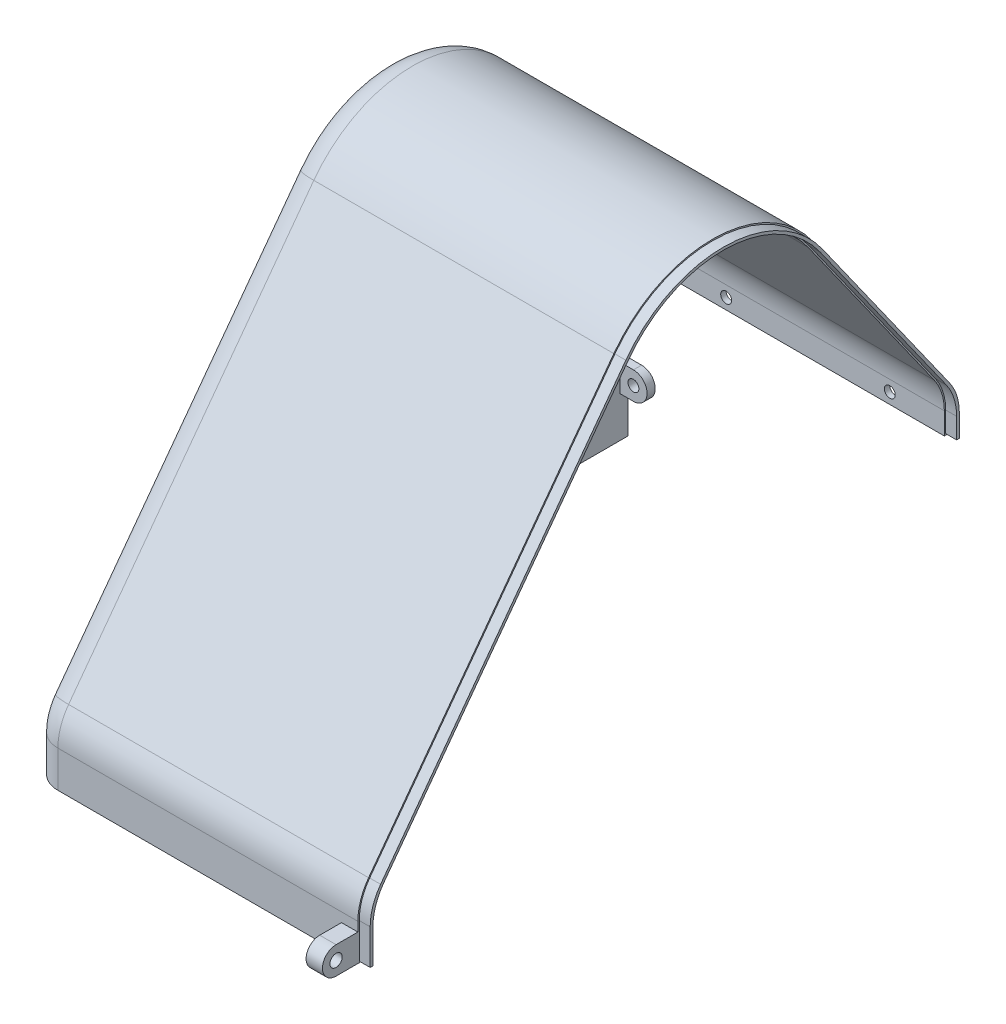
SolidWorks part; units mm, degrees
ref_plane "Alzado" through (0, 0, 0) normal (0, 0, 1) x (1, 0, 0)
ref_plane "Planta" through (0, 0, 0) normal (0, 1, 0) x (1, 0, 0)
ref_plane "Vista lateral" through (0, 0, 0) normal (1, 0, 0) x (0, 0, -1)
sketch "Croquis1" plane through (0, 0, 0) normal (1, 0, 0) x (0, 0, -1)
  line L0 (-200, 0) -> (200, 0)
  line L2 (17.0234, 70) -> (175, 70)
  line L3 (-200, 0) -> (-200, 20)
  line L4 (-200, 20) -> (-106.1703, 146.7714)
  line L5 (200, 0) -> (200, 45)
  line L6 (200, 45) -> (175, 70)
  line L7 (17.0234, 70) -> (17.0234, 75)
  line L8 (17.0234, 75) -> (-33.2796, 146.0118)
  arc A0 (-33.2796, 146.0118) -> (-106.1703, 146.7714) centre (-70, 120) ccw
  circle A1 centre (-70, 120) radius 12
  arc A3 (-106.1703, 146.7714) -> (-33.2796, 146.0118) centre (-70, 120) ccw construction
  point P3 (0, 0)
  dimension "D4" = 90
  dimension "D5" = 24
  dimension "D1" = 400
  dimension "D2" = 120
  dimension "D3" = 70
  dimension "D6" = 20
  dimension "D7" = 70
  dimension "D8" = 45
  dimension "D9" = 50.3031
  dimension "D10" = 45
  dimension "D11" = 5
extrude "Saliente-Extruir1" add sketch "Croquis1" along normal blind 120
sketch "Croquis2" plane through (120, 0, 0) normal (1, 0, 0) x (0, 0, -1)
  line L2 (200, 45) -> (175, 70) construction
  line L3 (35.0234, 60) -> (35.0234, 68)
  line L4 (35.0234, 68) -> (174.1716, 68)
  line L5 (175, 70) -> (17.0234, 70) construction
  line L7 (200, 0) -> (200, 45) construction
  line L8 (-198, 0) -> (-198, 19.3404)
  line L9 (-200, 0) -> (200, 0) construction
  line L20 (-198, 19.3404) -> (-104.5627, 145.5816)
  line L21 (-106.1703, 146.7714) -> (-200, 20) construction
  line L22 (-200, 20) -> (-200, 0) construction
  line L23 (-34.9117, 144.8557) -> (15.0234, 74.3634)
  line L24 (15.0234, 74.3634) -> (15.0234, 60)
  line L28 (15.0234, 60) -> (35.0234, 60)
  line L29 (174.1716, 68) -> (198, 44.1716)
  line L33 (198, 44.1716) -> (198, 0)
  line L34 (198, 0) -> (-198, 0)
  line L35 (17.0234, 70) -> (17.0234, 75) construction
  arc A8 (-34.9117, 144.8557) -> (-104.5627, 145.5816) centre (-70, 120) ccw
  arc A9 (-34.9117, 144.8557) -> (-104.5627, 145.5816) centre (-70, 120) ccw
  dimension "D2" = 2
  dimension "D3" = 2
  dimension "D4" = 2
  dimension "D5" = 2
  dimension "D6" = 2
  dimension "D7" = 10
  dimension "D8" = 20
  dimension "D1" = 2
extrude "Cortar-Extruir1" cut sketch "Croquis2" against normal offset from surface (118 mm away) 2 up to face at (0, 65.7099, -7.7545)
fillet "Redondeo1" radius 20 6 edges at (60, 45, -200) (60, 70, -175) (60, 20, 200) (61, 68, -174.1716) (61, 44.1716, -198) (61, 19.3404, 198)
sketch "Croquis3" plane through (0, 0, -17.0234) normal (0, 0, -1) x (-1, 0, 0)
  line L0 (0, 64.1421) -> (-120, 64.1421) construction
  line L1 (65, 189.1421) -> (-185, 189.1421)
  line L2 (65, 189.1421) -> (65, -60.8579)
  line L3 (65, -60.8579) -> (-185, -60.8579)
  line L4 (-185, 189.1421) -> (-185, -60.8579)
  line L5 (65, 189.1421) -> (-185, -60.8579) construction
  line L6 (65, -60.8579) -> (-185, 189.1421) construction
  point P0 (-60, 64.1421)
  dimension "D1" = 250
  dimension "D2" = 250
extrude "Cortar-Extruir2" cut sketch "Croquis3" along normal through all
sketch "Croquis4" plane through (0, 0, -17.0234) normal (0, 0, -1) x (-1, 0, 0)
  line L0 (-2, 60) -> (-120, 60) construction
  circle A0 centre (-100, 64) radius 2
  circle A1 centre (-40, 64) radius 2
  dimension "D1" = 4
  dimension "D2" = 4
  dimension "D3" = 60
  dimension "D4" = 40
  dimension "D8" = 4
extrude "Cortar-Extruir3" cut sketch "Croquis4" against normal blind 20
sketch "Croquis5" plane through (0, 0, -17.0234) normal (0, 0, -1) x (-1, 0, 0)
  line L0 (-2, 60) -> (-120, 60) construction
  circle A0 centre (-70, 64) radius 2
  circle A1 centre (-10, 64) radius 2
  circle A2 centre (-100, 64) radius 2 construction
  circle A3 centre (-40, 64) radius 2 construction
  dimension "D4" = 4
  dimension "D5" = 4
  dimension "D1" = 30
  dimension "D2" = 30
  dimension "D3" = 4
extrude "Saliente-Extruir2" add sketch "Croquis5" along normal blind 6
fillet "Redondeo2" radius 10 10 edges at (0, 110.5059, 8.1281) (0, 6.7018, 200) (0, 19.6681, 198.9936) (0, 86.0367, 151.123) (0, 164.9976, 69.5311) (2, 6.372, 198) (2, 19.0084, 196.9936) (2, 109.6096, 9.9441) (2, 162.9977, 69.5519) (2, 85.112, 149.3192)
fillet "Redondeo4" radius 20 2 edges at (65, 75, -17.0234) (66, 74.3634, -15.0234) tangent propagation no
sketch "Croquis6" plane through (120, 0, 0) normal (1, 0, 0) x (0, 0, -1)
  line L50 (16.5234, 60.5) -> (16.5234, 68.6339)
  line L51 (12.9356, 79.9057) -> (-33.6876, 145.7228)
  line L52 (-105.7684, 146.4739) -> (-195.6738, 25.0046)
  line L53 (-199.5, 13.4036) -> (-199.5, 0.5)
  line L54 (-199.5, 0.5) -> (-198.5, 0.5)
  line L55 (-198.5, 0.5) -> (-198.5, 12.744)
  line L56 (-194.4776, 24.9399) -> (-104.9646, 145.879)
  line L57 (-34.5037, 145.1448) -> (11.7516, 79.8472)
  line L58 (15.5234, 67.9973) -> (15.5234, 60.5)
  line L59 (15.5234, 60.5) -> (16.5234, 60.5)
  line L60 (16.5234, 60.5) -> (16.5234, 68.6339)
  line L61 (12.9356, 79.9057) -> (-33.6876, 145.7228)
  line L62 (-105.7684, 146.4739) -> (-195.6738, 25.0046)
  line L63 (-199.5, 13.4036) -> (-199.5, 0.5)
  line L64 (-199.5, 0.5) -> (-198.5, 0.5)
  line L65 (-198.5, 0.5) -> (-198.5, 12.744)
  line L66 (-194.4776, 24.9399) -> (-104.9646, 145.879)
  line L67 (-34.5037, 145.1448) -> (11.7516, 79.8472)
  line L68 (15.5234, 67.9973) -> (15.5234, 60.5)
  line L69 (15.5234, 60.5) -> (16.5234, 60.5)
  arc A25 (16.5234, 68.6339) -> (12.9356, 79.9057) centre (-2.9766, 68.6339) ccw
  arc A26 (-33.6876, 145.7228) -> (-105.7684, 146.4739) centre (-70, 120) ccw
  arc A27 (-195.6738, 25.0046) -> (-199.5, 13.4036) centre (-180, 13.4036) ccw
  arc A28 (-194.4776, 24.9399) -> (-198.5, 12.744) centre (-178, 12.744) ccw
  arc A29 (-34.5037, 145.1448) -> (-104.9646, 145.879) centre (-70, 120) ccw
  arc A30 (16.5234, 68.6339) -> (12.9356, 79.9057) centre (-2.9766, 68.6339) ccw
  arc A31 (-33.6876, 145.7228) -> (-105.7684, 146.4739) centre (-70, 120) ccw
  arc A32 (-195.6738, 25.0046) -> (-199.5, 13.4036) centre (-180, 13.4036) ccw
  arc A33 (-194.4776, 24.9399) -> (-198.5, 12.744) centre (-178, 12.744) ccw
  arc A34 (-34.5037, 145.1448) -> (-104.9646, 145.879) centre (-70, 120) ccw
  arc A36 (15.5234, 67.9973) -> (11.7516, 79.8472) centre (-4.9766, 67.9973) ccw
  arc A37 (15.5234, 67.9973) -> (11.7516, 79.8472) centre (-4.9766, 67.9973) ccw
  dimension "D1" = 0.5
extrude "Saliente-Extruir3" add sketch "Croquis6" along normal blind 4
sketch "Croquis7" plane through (0, 0, 0) normal (0, -1, 0) x (1, 0, 0)
  line L0 (2, 75) -> (5, 75)
  line L1 (2, 34.9117) -> (2, 104.5627) construction
  line L2 (5, 65) -> (2, 65)
  line L3 (2, 65) -> (2, 75)
  line L4 (0, 190) -> (0, -17.0234) construction
  circle A1 centre (5, 70) radius 2.25
  arc A2 (5, 75) -> (5, 65) centre (5, 70) cw
  dimension "D1" = 4.5
  dimension "D2" = 5
  dimension "D3" = 70
  dimension "D4" = 10
extrude "Saliente-Extruir4" add sketch "Croquis7" against normal blind 6
sketch "Croquis9" plane through (120, 0, 0) normal (1, 0, 0) x (0, 0, -1)
  line L0 (-200, 0) -> (-208, 0)
  line L1 (-200, 13.4036) -> (-200, 0) construction
  line L2 (-208, 10) -> (-200, 10)
  line L3 (-200, 10) -> (-200, 0)
  line L4 (-198, 12.744) -> (-198, 0) construction
  arc A0 (-208, 0) -> (-208, 10) centre (-208, 5) cw
  circle A1 centre (-208, 5) radius 2.25
  dimension "D3" = 4.5
  dimension "D1" = 10
  dimension "D2" = 10
extrude "Saliente-Extruir5" add sketch "Croquis9" against normal blind 6
sketch "Croquis10" plane through (0, 0, -17.0234) normal (0, 0, -1) x (-1, 0, 0)
  line L0 (-2, 15) -> (-7, 15)
  line L1 (-2, 24.6424) -> (-2, 12.744) construction
  line L2 (-7, 25) -> (-2, 25)
  line L3 (-2, 24.6424) -> (-2, 145.5816) construction
  line L4 (-2, 25) -> (-2, 15)
  line L5 (0, 0) -> (0, 57.7002) construction
  arc A0 (-7, 15) -> (-7, 25) centre (-7, 20) cw
  circle A1 centre (-7, 20) radius 2
  dimension "D1" = 4
  dimension "D2" = 10
  dimension "D3" = 20
  dimension "D4" = 7
extrude "Saliente-Extruir6" add sketch "Croquis10" against normal blind 3
fillet "Redondeo5" radius 5 1 edges at (0, 120, 58)
